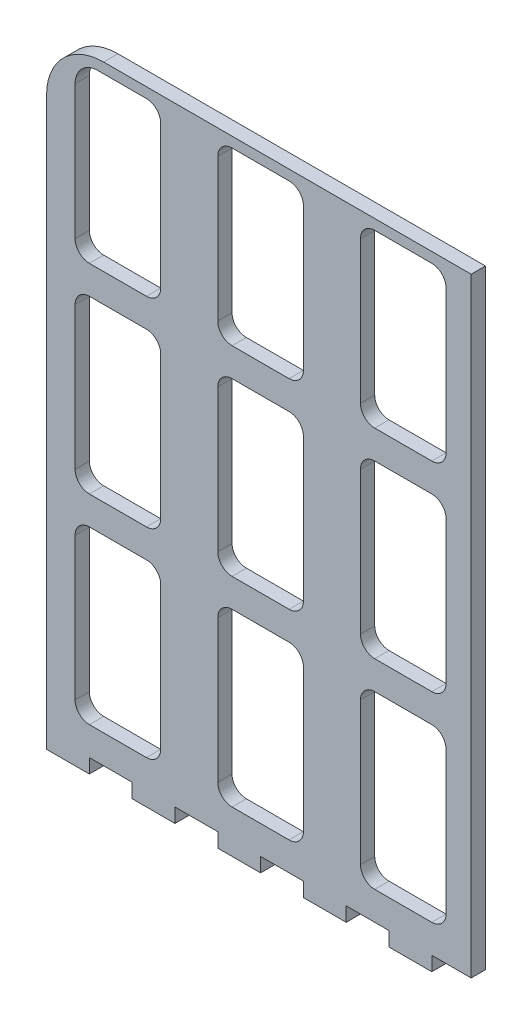
SolidWorks part; units mm, degrees
material "Balsa"
ref_plane "Front Plane" through (0, 0, 0) normal (0, 0, 1) x (1, 0, 0)
ref_plane "Top Plane" through (0, 0, 0) normal (0, 1, 0) x (1, 0, 0)
ref_plane "Right Plane" through (0, 0, 0) normal (1, 0, 0) x (0, 0, -1)
sketch "Sketch1" plane through (0, 0, 0) normal (0, 0, 1) x (1, 0, 0)
  line L1 (188.976, 0) -> (188.976, 271.272)
  line L2 (188.976, 271.272) -> (25.4, 271.272)
  line L4 (0, 0) -> (0, -6.35)
  line L6 (0, 0) -> (0, -6.35)
  line L7 (0, -6.35) -> (19.05, -6.35)
  line L8 (19.05, 0) -> (19.05, -6.35)
  line L10 (38.1, 0) -> (38.1, -6.35)
  line L11 (38.1, -6.35) -> (57.15, -6.35)
  line L12 (57.15, 0) -> (57.15, -6.35)
  line L14 (76.2, 0) -> (76.2, -6.35)
  line L15 (76.2, -6.35) -> (95.25, -6.35)
  line L16 (95.25, 0) -> (95.25, -6.35)
  line L18 (114.3, 0) -> (114.3, -6.35)
  line L19 (114.3, -6.35) -> (133.35, -6.35)
  line L20 (133.35, 0) -> (133.35, -6.35)
  line L22 (152.4, 0) -> (152.4, -6.35)
  line L23 (152.4, -6.35) -> (171.45, -6.35)
  line L24 (171.45, 0) -> (171.45, -6.35)
  line L25 (19.05, 0) -> (38.1, 0)
  line L26 (57.15, 0) -> (76.2, 0)
  line L27 (95.25, 0) -> (114.3, 0)
  line L28 (133.35, 0) -> (152.4, 0)
  line L29 (171.45, 0) -> (188.976, 0)
  line L30 (0, 245.872) -> (0, 0)
  line L31 (25.4, 271.272) -> (188.976, 271.272)
  line L32 (19.05, 0) -> (38.1, 0)
  line L33 (38.1, -6.35) -> (57.15, -6.35)
  line L34 (57.15, 0) -> (76.2, 0)
  arc A0 (25.4, 271.272) -> (0, 245.872) centre (25.4, 245.872) ccw
  point P8 (0, 271.272)
  point P11 (188.976, 271.272)
  dimension "D4" = 6.35
  dimension "D5" = 19.05
  dimension "D1" = 188.976
  dimension "D2" = 271.272
  dimension "D3" = 188.976
  dimension "D6" = 6.35
  dimension "D7" = 19.05
  dimension "D8" = 19.05
  dimension "D9" = 19.05
  dimension "D10" = 19.05
  dimension "D11" = 6.35
  dimension "D12" = 19.05
  dimension "D13" = 19.05
  dimension "D14" = 6.35
  dimension "D15" = 19.05
  dimension "D16" = 19.05
  dimension "D17" = 6.35
  dimension "D18" = 245.872
  dimension "D19" = 163.576
  dimension "D20" = 271.272
  dimension "D21" = 6.35
  dimension "D22" = 6.35
  dimension "D23" = 6.35
extrude "Boss-Extrude1" add sketch "Sketch1" along normal blind 6.35 contours L2 A0 L30 L4 L7 L8 L25 L10 L11 L12 L26 L14 L15 L16 L27 L18 L19 L20 L28 L22 L23 L24 L29 L1 region at (94.6232, 133.6652, 0)
sketch "Sketch2" plane through (0, 0, 6.35) normal (0, 0, 1) x (1, 0, 0)
  line L0 (0, 245.872) -> (0, -6.35) construction
  line L5 (44.45, 266.7) -> (22.86, 266.7)
  line L38 (76.2, 19.05) -> (76.2, 82.55)
  line L39 (19.05, 12.7) -> (44.45, 12.7)
  line L40 (188.976, 271.272) -> (25.4, 271.272) construction
  line L68 (12.7, 19.05) -> (12.7, 82.55)
  line L69 (19.05, 88.9) -> (44.45, 88.9)
  line L70 (50.8, 19.05) -> (50.8, 82.55)
  line L71 (82.55, 12.7) -> (107.95, 12.7)
  line L72 (114.3, 19.05) -> (114.3, 82.55)
  line L73 (82.55, 88.9) -> (107.95, 88.9)
  line L74 (139.7, 19.05) -> (139.7, 82.55)
  line L75 (146.05, 12.7) -> (171.45, 12.7)
  line L76 (177.8, 19.05) -> (177.8, 82.55)
  line L77 (146.05, 88.9) -> (171.45, 88.9)
  line L78 (76.2, 107.95) -> (76.2, 171.45)
  line L79 (82.55, 101.6) -> (107.95, 101.6)
  line L80 (114.3, 107.95) -> (114.3, 171.45)
  line L81 (82.55, 177.8) -> (107.95, 177.8)
  line L82 (139.7, 107.95) -> (139.7, 171.45)
  line L83 (146.05, 101.6) -> (171.45, 101.6)
  line L84 (177.8, 107.95) -> (177.8, 171.45)
  line L85 (146.05, 177.8) -> (171.45, 177.8)
  line L86 (76.2, 196.85) -> (76.2, 260.35)
  line L87 (82.55, 190.5) -> (107.95, 190.5)
  line L88 (114.3, 196.85) -> (114.3, 260.35)
  line L89 (82.55, 266.7) -> (107.95, 266.7)
  line L90 (139.7, 196.85) -> (139.7, 260.35)
  line L91 (146.05, 190.5) -> (171.45, 190.5)
  line L92 (177.8, 196.85) -> (177.8, 260.35)
  line L93 (146.05, 266.7) -> (171.45, 266.7)
  line L94 (12.7, 107.95) -> (12.7, 171.45)
  line L95 (19.05, 101.6) -> (44.45, 101.6)
  line L96 (50.8, 107.95) -> (50.8, 171.45)
  line L97 (19.05, 177.8) -> (44.45, 177.8)
  line L98 (12.7, 196.85) -> (12.7, 256.54)
  line L99 (19.05, 190.5) -> (44.45, 190.5)
  line L100 (50.8, 196.85) -> (50.8, 260.35)
  line L104 (19.05, 266.7) -> (44.45, 266.7) [skipped]
  arc A0 (139.7, 19.05) -> (146.05, 12.7) centre (146.05, 19.05) ccw
  arc A1 (171.45, 12.7) -> (177.8, 19.05) centre (171.45, 19.05) ccw
  arc A22 (177.8, 82.55) -> (171.45, 88.9) centre (171.45, 82.55) ccw
  arc A23 (139.7, 82.55) -> (146.05, 88.9) centre (146.05, 82.55) cw
  arc A24 (76.2, 82.55) -> (82.55, 88.9) centre (82.55, 82.55) cw
  arc A25 (114.3, 82.55) -> (107.95, 88.9) centre (107.95, 82.55) ccw
  arc A26 (107.95, 12.7) -> (114.3, 19.05) centre (107.95, 19.05) ccw
  arc A27 (76.2, 19.05) -> (82.55, 12.7) centre (82.55, 19.05) ccw
  arc A28 (44.45, 12.7) -> (50.8, 19.05) centre (44.45, 19.05) ccw
  arc A29 (44.45, 88.9) -> (50.8, 82.55) centre (44.45, 82.55) cw
  arc A30 (12.7, 82.55) -> (19.05, 88.9) centre (19.05, 82.55) cw
  arc A31 (19.05, 12.7) -> (12.7, 19.05) centre (19.05, 19.05) cw
  arc A32 (12.7, 107.95) -> (19.05, 101.6) centre (19.05, 107.95) ccw
  arc A33 (12.7, 171.45) -> (19.05, 177.8) centre (19.05, 171.45) cw
  arc A34 (50.8, 171.45) -> (44.45, 177.8) centre (44.45, 171.45) ccw
  arc A35 (44.45, 101.6) -> (50.8, 107.95) centre (44.45, 107.95) ccw
  arc A36 (76.2, 107.95) -> (82.55, 101.6) centre (82.55, 107.95) ccw
  arc A37 (76.2, 171.45) -> (82.55, 177.8) centre (82.55, 171.45) cw
  arc A38 (114.3, 171.45) -> (107.95, 177.8) centre (107.95, 171.45) ccw
  arc A39 (107.95, 101.6) -> (114.3, 107.95) centre (107.95, 107.95) ccw
  arc A40 (139.7, 107.95) -> (146.05, 101.6) centre (146.05, 107.95) ccw
  arc A41 (171.45, 101.6) -> (177.8, 107.95) centre (171.45, 107.95) ccw
  arc A42 (139.7, 171.45) -> (146.05, 177.8) centre (146.05, 171.45) cw
  arc A43 (177.8, 171.45) -> (171.45, 177.8) centre (171.45, 171.45) ccw
  arc A44 (177.8, 260.35) -> (171.45, 266.7) centre (171.45, 260.35) ccw
  arc A45 (171.45, 190.5) -> (177.8, 196.85) centre (171.45, 196.85) ccw
  arc A46 (139.7, 196.85) -> (146.05, 190.5) centre (146.05, 196.85) ccw
  arc A47 (139.7, 260.35) -> (146.05, 266.7) centre (146.05, 260.35) cw
  arc A48 (76.2, 260.35) -> (82.55, 266.7) centre (82.55, 260.35) cw
  arc A49 (114.3, 260.35) -> (107.95, 266.7) centre (107.95, 260.35) ccw
  arc A50 (107.95, 190.5) -> (114.3, 196.85) centre (107.95, 196.85) ccw
  arc A51 (76.2, 196.85) -> (82.55, 190.5) centre (82.55, 196.85) ccw
  arc A52 (12.7, 196.85) -> (19.05, 190.5) centre (19.05, 196.85) ccw
  arc A53 (44.45, 190.5) -> (50.8, 196.85) centre (44.45, 196.85) ccw
  arc A54 (50.8, 260.35) -> (44.45, 266.7) centre (44.45, 260.35) ccw
  arc A56 (22.86, 266.7) -> (12.7, 256.54) centre (22.86, 256.54) ccw
  point P88 (50.8, 12.7)
  point P93 (12.7, 88.9)
  point P96 (12.7, 12.7)
  dimension "D7" = 6.35
  dimension "D12" = 4.572
  dimension "D11" = 10.16
  dimension "D1" = 76.2
  dimension "D2" = 38.1
  dimension "D3" = 3
  dimension "D4" = 3
  dimension "D5" = 12.7
  dimension "D6" = 12.7
  dimension "D8" = 25.4
  dimension "D9" = 12.7
  dimension "D10" = 12.7
extrude "Cut-Extrude1" cut sketch "Sketch2" against normal through all
